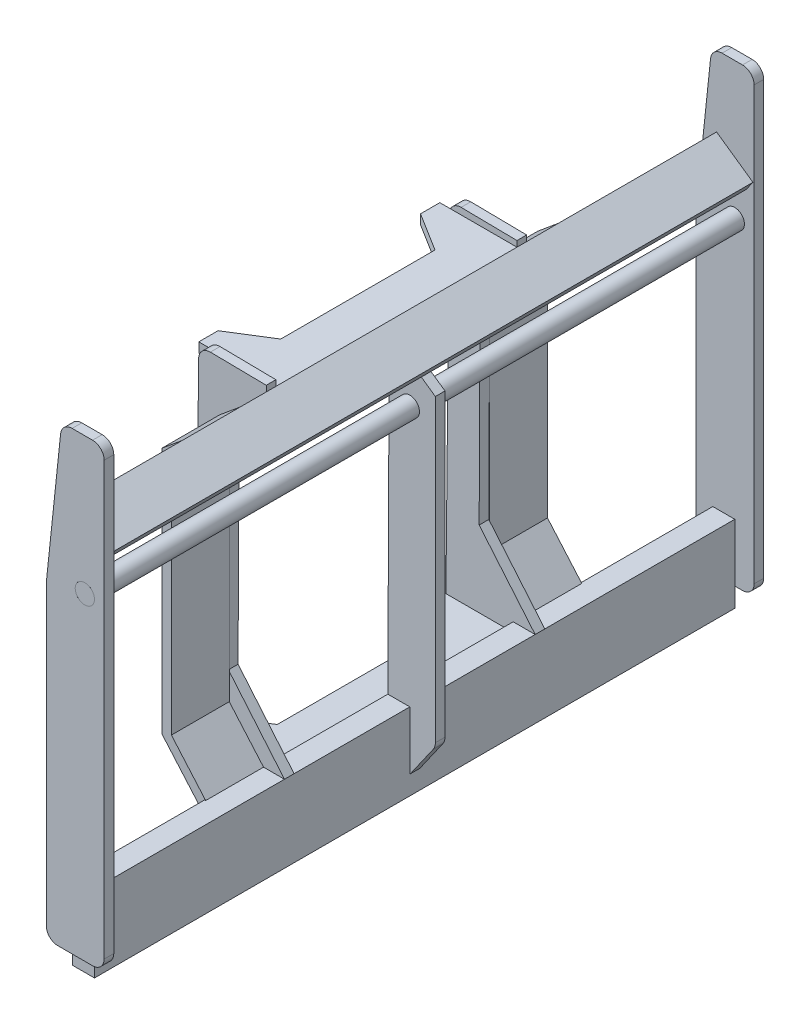
SolidWorks part; units mm, degrees
ref_plane "Front Plane" through (0, 0, 0) normal (0, 0, 1) x (1, 0, 0)
ref_plane "Top Plane" through (0, 0, 0) normal (0, 1, 0) x (1, 0, 0)
ref_plane "Right Plane" through (0, 0, 0) normal (1, 0, 0) x (0, 0, -1)
sketch "Sketch1" plane through (0, 0, 0) normal (0, 0, 1) x (1, 0, 0)
  line L0 (0, 0) -> (0, 1180)
  line L1 (0, 1180) -> (-110, 1180)
  line L2 (-110, 1180) -> (-150, 800)
  line L3 (-150, 800) -> (-150, 0)
  line L4 (-150, 0) -> (0, 0)
  dimension "D1" = 1180
  dimension "D2" = 150
  dimension "D3" = 800
  dimension "D4" = 110
extrude "Boss-Extrude2" add sketch "Sketch1" along normal blind 25 from offset 830
extrude "Boss-Extrude3" add sketch "Sketch1<2>" against normal blind 25 from offset 830 separate body offset against normal yes
sketch "Sketch1<2>" plane through (0, 0, 0) normal (0, 0, 1) x (1, 0, 0) same geometry as "Sketch1"
sketch "Sketch2" plane through (0, 0, -830) normal (0, 0, 1) x (1, 0, 0)
  line L0 (-3, 930) -> (-20.2073, 905.4254)
  line L1 (-50, -50) -> (-107, -50)
  line L2 (-50, -50) -> (-50, 150)
  line L3 (-50, 150) -> (-107, 150)
  line L4 (-107, -50) -> (-107, 150)
  line L5 (-3, 930) -> (-97.2025, 995.9613)
  line L6 (-20.2073, 905.4254) -> (-114.4098, 971.3867)
  line L7 (-97.2025, 995.9613) -> (-114.4098, 971.3867)
  line L8 (0, 0) -> (0, 1180) construction
  line L9 (0, 1180) -> (-110, 1180) construction
  line L11 (-150, 0) -> (0, 0) construction
  dimension "D1" = 30
  dimension "D2" = 3
  dimension "D3" = 115
  dimension "D4" = 55
  dimension "D5" = 250
  dimension "D6" = 57
  dimension "D7" = 50
  dimension "D8" = 150
  dimension "D9" = 200
extrude "Boss-Extrude4" add sketch "Sketch2" along normal up to surface (1660 mm away) up to face at (-82, 632, 830)
sketch "Sketch3" plane through (0, 0, 0) normal (0, 0, 1) x (1, 0, 0)
  line L0 (-103.4153, 963.6883) -> (16.2168, 879.921)
  line L2 (16.2168, 879.921) -> (16.2168, 93.0953)
  line L3 (16.2168, 93.0953) -> (-48.9668, 0.0036)
  line L4 (-50, 0) -> (0, 0) construction
  line L5 (-48.9668, 0.0036) -> (-50, 150)
  line L6 (-50, 150) -> (-107, 150)
  line L7 (-107, 150) -> (-103.4153, 963.6883)
  line L8 (-114.4098, 971.3867) -> (-20.2073, 905.4254) construction
  dimension "D1" = 120
  dimension "D2" = 150
  dimension "D3" = 55
  dimension "D4" = 0
extrude "Boss-Extrude5" add sketch "Sketch3" along normal mid plane 25
sketch "Sketch4" plane through (0, 0, 855) normal (0, 0, 1) x (1, 0, 0)
  line L0 (0, 0) -> (0, 1180) construction
  line L1 (0, 1180) -> (-110, 1180) construction
  circle A0 centre (-50, 825) radius 25
  point P6 (-55, 1180)
  dimension "D1" = 50
  dimension "D2" = 50
  dimension "D3" = 355
extrude "Cut-Extrude1" cut sketch "Sketch4" against normal through all
sketch "Sketch5" plane through (0, 0, 855) normal (0, 0, 1) x (1, 0, 0)
  circle A2 centre (-50, 825) radius 24.99
  circle A3 centre (-50, 825) radius 24.99
  dimension "D1" = 0.01
extrude "Boss-Extrude6" add sketch "Sketch5" against normal up to surface (1710 mm away) separate body up to face at (-25, 825, -855)
sketch "Sketch6" plane through (0, 0, -12.5) normal (0, 0, -1) x (-1, 0, 0)
  line L0 (50, 150) -> (107, 150) construction
  line L1 (50, 150) -> (107, 150)
  line L2 (97.2025, 995.9613) -> (114.4098, 971.3867) construction
  line L3 (97.2025, 995.9613) -> (114.4098, 971.3867)
  line L4 (114.4098, 971.3867) -> (20.2073, 905.4254) construction
  line L5 (114.4098, 971.3867) -> (67.3085, 938.4061)
  line L6 (107, 150) -> (107.0015, 75.4933)
  line L8 (97.2025, 1010.9613) -> (272.2025, 1013.3903)
  line L9 (272.2025, 1013.3903) -> (282, 75.4933)
  line L10 (282, 75.4933) -> (107.0015, 75.4933)
  line L11 (97.2025, 1010.9613) -> (97.2025, 995.9613)
  line L12 (67.3085, 938.4061) -> (193.0263, 825.2093)
  line L13 (193.0263, 825.2093) -> (195.2383, 323.0883)
  line L14 (195.2383, 323.0883) -> (50, 150)
  line L20 (103.4153, 963.6883) -> (107, 150) construction
  dimension "D1" = 89
  dimension "D2" = 89
  dimension "D3" = 175
  dimension "D4" = 77
  dimension "D5" = 50
  dimension "D6" = 15
  dimension "D8" = 937.9482
extrude "Boss-Extrude9" add sketch "Sketch6" along normal blind 25 from offset 300
sketch "Sketch11" plane through (0, 0, -337.5) normal (0, 0, -1) x (-1, 0, 0)
  line L0 (112.3388, 939.4817) -> (193.0978, 872.3375)
  line L2 (193.0978, 872.3375) -> (193.0978, 252.6073)
  line L4 (104.1526, 149.894) -> (193.0978, 252.6073)
extrude "Extrude-Thin11" add sketch "Sketch11" along normal blind 150 thin thin type one direction wall 25
sketch "Sketch12" plane through (395.4236, 328.7612, 0) normal (0.7689, 0.6393, 0) x (0, 0, -1)
  line L4 (337.5, 819.2305) -> (337.5, 794.2305)
  line L5 (337.5, 794.2305) -> (487.5, 794.2305)
  line L6 (487.5, 794.2305) -> (487.5, 819.2305)
  line L7 (487.5, 819.2305) -> (337.5, 819.2305)
  line L8 (337.5, 819.2305) -> (337.5, 794.2305)
  line L9 (337.5, 794.2305) -> (487.5, 794.2305)
  line L10 (487.5, 794.2305) -> (487.5, 819.2305)
  line L11 (487.5, 819.2305) -> (337.5, 819.2305)
  dimension "D1" = 0
extrude "Boss-Extrude10" add sketch "Sketch12" along normal up to next
mirror "Mirror1" about plane through (0, 0, 0) normal (0, 0, 1) of "Boss-Extrude9", "Extrude-Thin11"
ref_plane "Plane1" through (0, 995.9613, 0) normal (0, 1, 0) x (1, 0, 0)
sketch "Sketch13" plane through (0, 995.9613, 0) normal (0, 1, 0) x (1, 0, 0)
  line L0 (-297.2025, 312.5) -> (-97.2025, 312.5)
  line L1 (-272.2025, 312.5) -> (-97.2025, 312.5) construction
  line L2 (-97.2025, 312.5) -> (-97.2025, -312.5)
  line L3 (-97.2025, -312.5) -> (-297.2025, -312.5)
  line L4 (-272.2025, -312.5) -> (-97.2025, -312.5) construction
  line L5 (-297.2025, -312.5) -> (-297.2025, -262.5)
  line L6 (-297.2025, -262.5) -> (-197.2025, -200)
  line L7 (-197.2025, -200) -> (-197.2025, 200)
  line L8 (-197.2025, 200) -> (-297.2025, 262.5)
  line L9 (-297.2025, 262.5) -> (-297.2025, 312.5)
  line L10 (0, 0) -> (-921.1265, 0) construction
  dimension "D1" = 100
  dimension "D2" = 50
  dimension "D3" = 400
  dimension "D4" = 200
extrude "Boss-Extrude11" add sketch "Sketch13" against normal blind 25
pattern_linear "LPattern1" count 2 spacing 870 along (-0.0104, -0.9999, 0) of "Boss-Extrude11"
fillet "Fillet1" radius 30 13 edges at (16.2168, 93.0953, 0) (0, 0, -842.5) (0, 0, 842.5) (0, 1180, -842.5) (-110, 1180, -842.5) (-272.2025, 1013.3903, -325) (-272.2025, 1013.3903, 325) (0, 1180, 842.5) (-110, 1180, 842.5) (-150, 0, 842.5) (-150, 0, -842.5) (-282, 75.4933, 325) (-282, 75.4933, -325)
